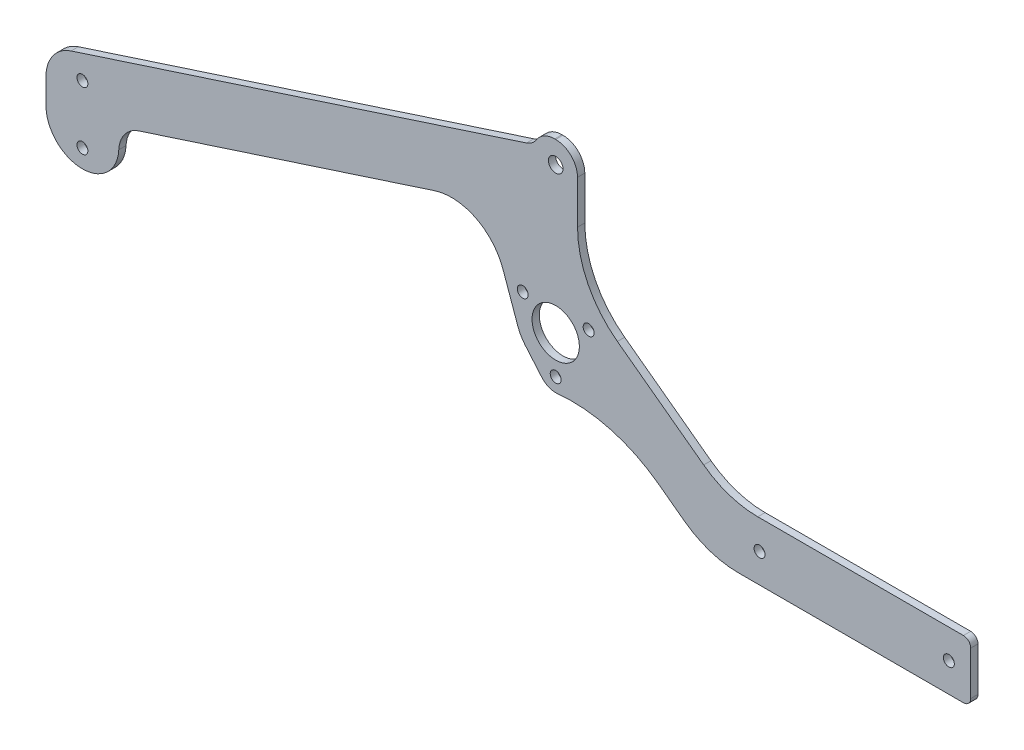
SolidWorks part; units mm, degrees
ref_plane "Спереди" through (0, 0, 0) normal (0, 0, 1) x (1, 0, 0)
ref_plane "Сверху" through (0, 0, 0) normal (0, 1, 0) x (1, 0, 0)
ref_plane "Справа" through (0, 0, 0) normal (1, 0, 0) x (0, 0, -1)
sketch "эскиз" plane through (0, 0, 0) normal (0, 0, 1) x (1, 0, 0)
  line L0 (90, -110) -> (90, -24) construction
  line L1 (-55, -110) -> (-55, -24) construction
  line L2 (-200, -24) -> (-166, -24) construction
  line L3 (-200, -110) -> (-55, -110) construction
  line L4 (-200, -24) -> (-218, -24) construction
  line L5 (-55, -110) -> (90, -110) construction
  line L6 (-200, -110) -> (-200, -24) construction
  line L7 (56, -24) -> (90, -24) construction
  line L8 (108, -24) -> (90, -24) construction
  line L9 (-257.5, -110) -> (147.5, -110) construction
  line L10 (-200, -24) -> (-130, -24) construction
  line L11 (-130, -24) -> (-55, -24) construction
  line L12 (-130, -24) -> (0, 0) construction
  line L13 (0, 0) -> (90, -24) construction
  line L14 (-130, -24) -> (-130, -5) construction
  circle A0 centre (-200, -110) radius 57.5 construction
  circle A1 centre (-55, -110) radius 57.5 construction
  circle A2 centre (90, -110) radius 57.5 construction
  circle A3 centre (-218, -24) radius 1.5 construction
  circle A4 centre (-166, -24) radius 1.5 construction
  circle A5 centre (56, -24) radius 1.5 construction
  circle A6 centre (108, -24) radius 1.5 construction
  circle A7 centre (-89, -24) radius 1.5 construction
  circle A8 centre (-37, -24) radius 1.5 construction
  circle A9 centre (-130, -5) radius 1.5
  circle A10 centre (-130, -21) radius 1.5
  circle A11 centre (-130, -36) radius 2
  circle A12 centre (0, 40) radius 2
  point P31 (-183, -24)
  dimension "D1" = 115
  dimension "D4" = 3
  dimension "D7" = 34
  dimension "D12" = 3
  dimension "D11" = 4
  dimension "D17" = 4
  dimension "D19" = 18
  dimension "D2" = 145
  dimension "D3" = 86
  dimension "D5" = 18
  dimension "D6" = 34
  dimension "D8" = 70
  dimension "D9" = 145
  dimension "D10" = 55
  dimension "D13" = 16
  dimension "D14" = 12
  dimension "D15" = 110
  dimension "D16" = 15
  dimension "D18" = 40
sketch "эскиз 1" plane through (0, 0, 0) normal (0, 0, 1) x (1, 0, 0)
  line L0 (-224, -16) -> (-224, -32)
  line L1 (-224, -32) -> (-154, -32)
  line L2 (-154, -32) -> (-154, -47)
  line L3 (-224, -16) -> (-146.1949, -16)
  line L4 (-55, -110) -> (90, -110) construction
  line L5 (-31, -32) -> (-31, -16)
  line L6 (-154, -47) -> (-106, -47)
  line L9 (-136.245, -27) -> (-123.755, -27)
  line L10 (-106, -32) -> (-106, -47)
  line L11 (-55, -16) -> (-55, -110) construction
  line L12 (-106, -32) -> (-31, -32)
  line L13 (-31, -32) -> (-106, -32)
  line L14 (-140, -26) -> (-120, -26) construction
  line L15 (-113.8051, -16) -> (-31, -16)
  line L16 (-130, -24) -> (-130, -5) construction
  line L17 (-55, -110) -> (-55, -24) construction
  line L18 (-200, -16) -> (-200, -32) construction
  line L19 (-200, -110) -> (-200, -24) construction
  line L20 (-200, -24) -> (-218, -24) construction
  line L21 (-130, -27) -> (-130, -47) construction
  line L22 (-140, -27) -> (-140, -16) construction
  line L23 (-120, -26.2682) -> (-120, -16) construction
  line L24 (-146.1949, -16) -> (-146.1949, -27) construction
  line L25 (-146.1949, -27) -> (-113.8051, -27) construction
  line L26 (-113.8051, -27) -> (-113.8051, -16) construction
  circle A0 centre (-218, -24) radius 1.5
  circle A1 centre (-166, -24) radius 1.5
  circle A2 centre (-130, -36) radius 2
  circle A3 centre (-89, -24) radius 1.5
  circle A4 centre (-37, -24) radius 1.5
  circle A5 centre (-37, -24) radius 1.5 construction
  circle A6 centre (-89, -24) radius 1.5 construction
  circle A7 centre (-130, -36) radius 2 construction
  circle A8 centre (-166, -24) radius 1.5 construction
  circle A9 centre (-218, -24) radius 1.5 construction
  circle A10 centre (-130, -16) radius 10 construction
  circle A11 centre (-130, -36) radius 20 construction
  arc A12 (-123.755, -27) -> (-113.8051, -16) centre (-123.755, -17) ccw
  arc A13 (-136.245, -27) -> (-146.1949, -16) centre (-136.245, -17) cw
  point P25 (-130, -47)
  dimension "D6" = 9
  dimension "D5" = 20
  dimension "D1" = 24
  dimension "D2" = 24
  dimension "D3" = 16
  dimension "D4" = 11
  dimension "D7" = 70
  dimension "D8" = 8
  dimension "D9" = 5
extrude "тело маленькой арки" [suppressed] add sketch "эскиз 1" along normal blind 2
fillet "Скругление2" [suppressed] radius 10
fillet "Скругление3" [suppressed] radius 15
fillet "Скругление16" [suppressed] radius 8
fillet "Скругление18" [suppressed] radius 2
sketch "Эскиз1" plane through (0, 0, 0) normal (0, 0, 1) x (1, 0, 0)
  line L0 (6, 14.5175) -> (47.2728, -16)
  line L1 (47.2728, -16) -> (114, -16)
  line L2 (114, -16) -> (114, -32)
  line L3 (114, -32) -> (42, -32)
  line L4 (42, -32) -> (8.372, -7.1351)
  line L5 (-12.7222, 2.951) -> (-10.3652, -3.6828) construction
  line L6 (-10.3652, -3.6828) -> (-19.3787, 21.6857)
  line L7 (6, 14.5175) -> (6, 46)
  line L8 (-133.0902, 0.5106) -> (-6, 41.8047)
  line L9 (-140, -16) -> (-140, -9)
  line L10 (50, -16) -> (50, -32) construction
  line L11 (-120, -11.0081) -> (-19.3787, 21.6857)
  line L12 (-8.9167, 9.5422) -> (-1.9932, 10.8179) construction
  line L13 (90, -110) -> (90, -24) construction
  line L14 (3.8054, -12.4932) -> (8.372, -7.1351)
  line L15 (-3.8054, -12.4932) -> (-8.372, -7.1351)
  line L16 (-140, -26) -> (-120, -26) construction
  line L17 (-120, -16) -> (-120, -11.0081)
  line L18 (-130, -5) -> (-130, -26) construction
  line L19 (-130, -24) -> (-130, -5) construction
  line L20 (8.9167, 9.5422) -> (1.9932, 10.8179) construction
  line L21 (-120, -26) -> (-120, -16) construction
  line L22 (6, 46) -> (-6, 46)
  line L23 (-140, 1) -> (-120, 1) construction
  line L24 (-6, 46) -> (-6, 41.8047)
  line L27 (12.7222, 2.951) -> (10.3652, -3.6828) construction
  line L31 (-140, -16) -> (-140, -26) construction
  line L32 (-12.7222, 2.951) -> (-10.3652, -3.6828) [skipped]
  circle A0 centre (-130, -21) radius 1.5
  circle A1 centre (-130, -5) radius 1.5
  circle A2 centre (-130, -5) radius 1.5 construction
  circle A3 centre (-130, -21) radius 1.5 construction
  circle A4 centre (0, 0) radius 6.5
  circle A5 centre (0, 0) radius 11 construction
  arc A6 (-8.9167, 9.5422) -> (-12.7222, 2.951) centre (-8.0107, 4.625) ccw construction
  arc A7 (1.9932, 10.8179) -> (-1.9932, 10.8179) centre (0, 0) ccw construction
  arc A8 (-3.8054, -12.4932) -> (3.8054, -12.4932) centre (0, -9.25) ccw
  arc A9 (12.7222, 2.951) -> (8.9167, 9.5422) centre (8.0107, 4.625) ccw construction
  arc A10 (8.372, -7.1351) -> (10.3652, -3.6828) centre (0, 0) ccw construction
  arc A11 (-8.372, -7.1351) -> (-10.3652, -3.6828) centre (0, 0) cw
  circle A12 centre (0, 0) radius 9.25 construction
  circle A13 centre (0, -10.45) radius 1.5
  circle A14 centre (-9.05, 5.225) radius 1.5
  circle A15 centre (9.05, 5.225) radius 1.5
  circle A16 centre (0, 0) radius 7.65 construction
  circle A17 centre (108, -24) radius 1.5
  circle A18 centre (56, -24) radius 1.5
  circle A19 centre (56, -24) radius 1.5 construction
  circle A20 centre (108, -24) radius 1.5 construction
  circle A21 centre (0, 40) radius 2
  circle A22 centre (0, 40) radius 2 construction
  arc A23 (-140, -16) -> (-120, -16) centre (-130, -16) ccw
  arc A24 (-133.0902, 0.5106) -> (-140, -9) centre (-130, -9) ccw
  circle A25 centre (50, -7.7247) radius 24.2753 construction
  point P27 (114, -24)
  point P33 (0, 46)
  point P62 (0, 0)
  point P68 (0, 0)
  dimension "D2" = 13
  dimension "D3" = 3
  dimension "D5" = 5
  dimension "D6" = 18.5
  dimension "D7" = 22
  dimension "D14" = 3
  dimension "D17" = 15.3
  dimension "D18" = 6
  dimension "D20" = 12
  dimension "D13" = 6
  dimension "D22" = 20
  dimension "D4" = 18
  dimension "D11" = 6
  dimension "D16" = 16
  dimension "D9" = 8
  dimension "D1" = 16
  dimension "D8" = 10
  dimension "D10" = 24
  dimension "D12" = 15
  dimension "D15" = 3
  dimension "D19" = 10.45
  dimension "D21" = 5
extrude "тело большой арки" add sketch "Эскиз1" along normal blind 2
fillet "Скругление7" radius 15 1 edges at (-19.3787, 21.6857, 1)
fillet "Скругление8" radius 40 1 edges at (8.372, -7.1351, 1)
fillet "Скругление20" radius 6 2 edges at (6, 46, 1) (-6, 46, 1)
fillet "Скругление10" radius 27 1 edges at (6, 14.5175, 1)
fillet "Скругление17" radius 8 1 edges at (-120, -11.0081, 1)
fillet "Скругление21" radius 5 1 edges at (-6, 41.8047, 1)
fillet "Скругление23" radius 2 2 edges at (114, -32, 1) (114, -16, 1)
fillet "Скругление25" radius 25 2 edges at (47.2728, -16, 1) (42, -32, 1)
sketch "Эскиз6" [suppressed] plane through (0, 0, 2) normal (0, 0, 1) x (1, 0, 0)
  line L0 (-6.6599, 41.5903) -> (-133.0902, 0.5106) construction
  line L1 (5, 40) -> (5, 30.033)
  line L2 (-6.6599, 41.5903) -> (-19.6379, 37.3734)
  line L3 (-6.6599, 41.5903) -> (-133.0902, 0.5106) construction
  arc A0 (5.8569, 23.5437) -> (-19.6379, 37.3734) centre (-13.4576, 18.3523) ccw
  arc A1 (5, 30.033) -> (17.1801, 8.5703) centre (30, 30.033) ccw construction
  arc A2 (-6.6599, 41.5903) -> (-4.3406, 43.1728) centre (-8.205, 46.3455) ccw
  arc A3 (5, 30.033) -> (5.8569, 23.5437) centre (30, 30.033) ccw
  arc A4 (5, 40) -> (-0.2381, 44.9943) centre (0, 40) ccw
  arc A5 (5, 40) -> (0, 45) centre (0, 40) ccw construction
  arc A8 (-0.2381, 44.9943) -> (-4.3406, 43.1728) centre (-0.4762, 40) ccw
  arc A9 (-0.4762, 45) -> (-4.3406, 43.1728) centre (-0.4762, 40) ccw construction
  arc A10 (-6.6599, 41.5903) -> (-4.3406, 43.1728) centre (-8.205, 46.3455) ccw construction
  dimension "D1" = 20
extrude "Срез крепления тяги на внешней пластине" [suppressed] cut sketch "Эскиз6" against normal through all
sketch "Эскиз5" [suppressed] plane through (0, 0, 0) normal (0, 0, 1) x (1, 0, 0)
  line L11 (5, 15.8455) -> (51.1535, -16)
  line L14 (51.1535, -16) -> (114, -16)
  line L16 (114, -16) -> (114, -32)
  line L17 (114, -32) -> (44.4084, -32)
  line L18 (44.4084, -32) -> (8.372, -7.1351)
  line L20 (-12.7222, 2.951) -> (-20.3627, 24.4555)
  line L22 (5, 15.8455) -> (5, 50)
  line L23 (-133.4202, 1.3969) -> (-15, 44.4984)
  line L24 (-140, -16) -> (-140, -8)
  line L25 (-12.7222, 2.951) -> (-10.3652, -3.6828)
  line L26 (-120, -11.8095) -> (-20.3627, 24.4555)
  line L27 (-8.9167, 9.5422) -> (-1.9932, 10.8179) construction
  line L28 (3.8054, -12.4932) -> (8.372, -7.1351)
  line L29 (-3.8054, -12.4932) -> (-8.372, -7.1351)
  line L30 (-140, -26) -> (-120, -26) construction
  line L31 (-120, -16) -> (-120, -11.8095)
  line L32 (-130, -5) -> (-130, -26) construction
  line L33 (8.9167, 9.5422) -> (1.9932, 10.8179) construction
  line L34 (-120, -26) -> (-120, -16) construction
  line L35 (5, 50) -> (-15, 50)
  line L36 (-140, 2) -> (-120, 2) construction
  line L37 (-15, 50) -> (-15, 44.4984)
  line L38 (12.7222, 2.951) -> (10.3652, -3.6828) construction
  line L39 (-140, -16) -> (-140, -26) construction
  circle A3 centre (-130, -21) radius 1.5
  circle A4 centre (-130, -5) radius 1.5
  circle A5 centre (0, 0) radius 6.5
  circle A7 centre (0, 0) radius 11 construction
  arc A8 (-8.9167, 9.5422) -> (-12.7222, 2.951) centre (-8.0107, 4.625) ccw construction
  arc A10 (1.9932, 10.8179) -> (-1.9932, 10.8179) centre (0, 0) ccw construction
  arc A14 (-3.8054, -12.4932) -> (3.8054, -12.4932) centre (0, -9.25) ccw
  arc A20 (12.7222, 2.951) -> (8.9167, 9.5422) centre (8.0107, 4.625) ccw construction
  arc A21 (8.372, -7.1351) -> (10.3652, -3.6828) centre (0, 0) ccw construction
  arc A22 (-10.3652, -3.6828) -> (-8.372, -7.1351) centre (0, 0) ccw
  circle A23 centre (0, 0) radius 9.25 construction
  circle A24 centre (0, -10.45) radius 1.5
  circle A25 centre (-9.05, 5.225) radius 1.5
  circle A26 centre (9.05, 5.225) radius 1.5
  circle A27 centre (0, 0) radius 7.65 construction
  circle A28 centre (108, -24) radius 1.5
  circle A29 centre (56, -24) radius 1.5
  circle A30 centre (0, 40) radius 2
  arc A31 (-140, -16) -> (-120, -16) centre (-130, -16) ccw
  arc A32 (-133.4202, 1.3969) -> (-140, -8) centre (-130, -8) ccw
  point P48 (0, 0)
  point P52 (0, 0)
  dimension "D2" = 13
  dimension "D3" = 5
  dimension "D4" = 18.5
  dimension "D5" = 22
  dimension "D6" = 3
  dimension "D7" = 15.3
  dimension "D16" = 20
  dimension "D18" = 3
  dimension "D20" = 4
  dimension "D21" = 3
  dimension "D1" = 16
  dimension "D8" = 10.45
  dimension "D9" = 20
  dimension "D10" = 5
  dimension "D11" = 10
  dimension "D12" = 17
  dimension "D13" = 10
  dimension "D14" = 17
  dimension "D15" = 7
  dimension "D17" = 20
  dimension "D19" = 16
extrude "Тело внешней большой арки" [suppressed] add sketch "Эскиз5" along normal blind 2
